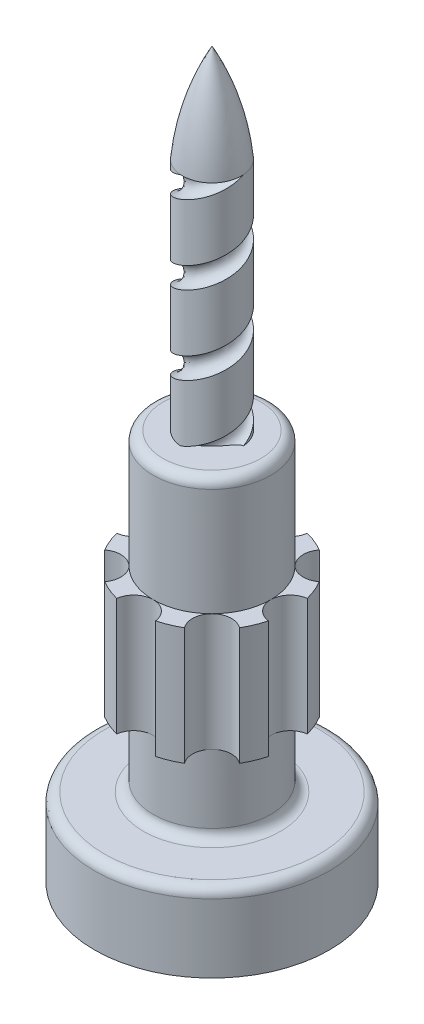
SolidWorks part; units mm, degrees
ref_plane "Front Plane" through (0, 0, 0) normal (0, 0, 1) x (1, 0, 0)
ref_plane "Top Plane" through (0, 0, 0) normal (0, 1, 0) x (1, 0, 0)
ref_plane "Right Plane" through (0, 0, 0) normal (1, 0, 0) x (0, 0, -1)
sketch "Sketch1" plane through (0, 0, 0) normal (0, 1, 0) x (1, 0, 0)
  circle A0 centre (0, 0) radius 30
  dimension "D1" = 60
extrude "Boss-Extrude1" add sketch "Sketch1" along normal blind 20
sketch "Sketch2" plane through (0, 20, 0) normal (0, 1, 0) x (1, 0, 0)
  circle A0 centre (0, 0) radius 15
  dimension "D1" = 30
extrude "Boss-Extrude2" add sketch "Sketch2" along normal blind 20
sketch "Sketch3" plane through (0, 40, 0) normal (0, 1, 0) x (1, 0, 0)
  circle A0 centre (0, 0) radius 20
  dimension "D1" = 40
extrude "Boss-Extrude3" add sketch "Sketch3" along normal blind 30
sketch "Sketch6" plane through (0, 70, 0) normal (0, 1, 0) x (1, 0, 0)
  circle A0 centre (0, 20) radius 5
  circle A1 centre (0, 0) radius 20 construction
  dimension "D1" = 10
extrude "Cut-Extrude1" cut sketch "Sketch6" against normal blind 40
pattern_circular "CirPattern1" count 8 over 360 about axis through (0, 70, 0) along (0, -1, 0) of "Cut-Extrude1"
sketch "Sketch7" plane through (0, 70, 0) normal (0, 1, 0) x (1, 0, 0)
  circle A0 centre (0, 0) radius 15
extrude "Boss-Extrude4" add sketch "Sketch7" along normal blind 30
sketch "Sketch8" plane through (0, 100, 0) normal (0, 1, 0) x (1, 0, 0)
  circle A0 centre (0, 0) radius 7.5
  dimension "D1" = 15
extrude "Boss-Extrude5" add sketch "Sketch8" along normal blind 60
fillet "Fillet1" radius 2.5 3 edges at (0, 100, 15) (0, 20, 30) (0, 20, 15)
sketch "Sketch9" plane through (0, 160, 0) normal (0, 1, 0) x (1, 0, 0)
  circle A0 centre (0, 0) radius 7.5 construction
  circle A1 centre (0, 0) radius 7.5
curve "Helix/Spiral1" pitch 20 height 60 radius 7.5 centre (0, 160, 0) axis (0, -1, 0) start towards (0.7071, 0, 0.7071)
ref_plane "Plane1" through (5.3033, 100, 5.3033) normal (-0.6509, -0.3907, 0.6509) x (0.5581, 0.335, 0.7592)
sketch "Sketch11" plane through (5.3033, 100, 5.3033) normal (-0.6509, -0.3907, 0.6509) x (0.5581, 0.335, 0.7592)
  circle A0 centre (0, 0) radius 2.5
  dimension "D1" = 5
sweep "Cut-Sweep1" cut profiles "Sketch11" path "Helix/Spiral1" align with end faces yes
sketch "Sketch12" plane through (0, 0, 0) normal (0, 0, 1) x (1, 0, 0)
  line L0 (0, 160) -> (0, 185)
  line L1 (-7.5, 160) -> (0, 160)
  line L2 (0, 97.5) -> (0, 212.1838) construction
  line L4 (-15, 97.5) -> (15, 97.5) construction
  arc A0 (-7.5, 160) -> (0, 185) centre (57.241, 154.2027) cw
  dimension "D1" = 65
  dimension "D2" = 25
revolve "Revolve1" add sketch "Sketch12" angle 360 about L2
